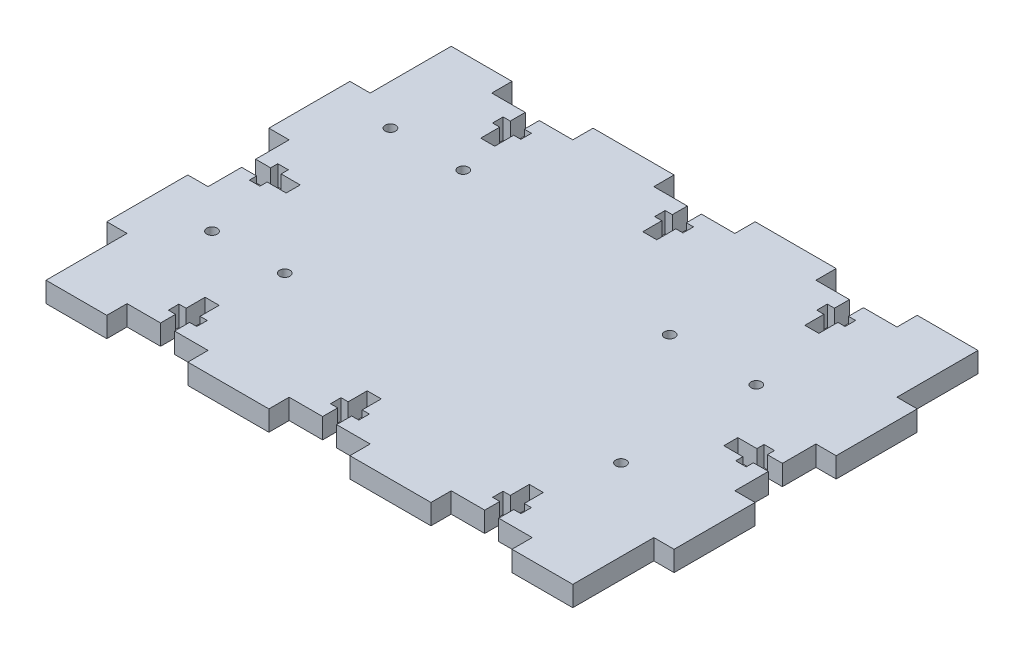
SolidWorks part; units mm, degrees
ref_plane "Front Plane" through (0, 0, 0) normal (0, 0, 1) x (1, 0, 0)
ref_plane "Top Plane" through (0, 0, 0) normal (0, 1, 0) x (1, 0, 0)
ref_plane "Right Plane" through (0, 0, 0) normal (1, 0, 0) x (0, 0, -1)
sketch "Sketch1" plane through (0, 0, 0) normal (0, 1, 0) x (1, 0, 0)
  line L1 (0, 0) -> (177.8, 0)
  line L2 (0, 0) -> (0, 127)
  line L3 (0, 127) -> (177.8, 127)
  line L4 (177.8, 0) -> (177.8, 127)
  dimension "D1" = 127
  dimension "D2" = 177.8
extrude "Boss-Extrude1" add sketch "Sketch1" along normal blind 6.35
sketch "Sketch2" plane through (0, 6.35, 0) normal (0, 1, 0) x (1, 0, 0)
  line L1 (0, 127) -> (6.35, 127)
  line L2 (0, 127) -> (0, 101.6)
  line L3 (0, 101.6) -> (6.35, 101.6)
  line L4 (6.35, 127) -> (6.35, 101.6)
  dimension "D1" = 25.4
  dimension "D2" = 6.35
extrude "Cut-Extrude1" cut sketch "Sketch2" against normal blind 6.35
pattern_linear "LPattern1" count 3 spacing 50.8 along (0, 0, 1) count 2 spacing 171.45 along (1, 0, 0) of "Cut-Extrude1"
sketch "Sketch3" plane through (0, 6.35, 0) normal (0, 1, 0) x (1, 0, 0)
  line L0 (6.35, 0) -> (171.45, 0) construction
  line L1 (25.4, 0) -> (50.8, 0)
  line L2 (25.4, 0) -> (25.4, 6.35)
  line L3 (25.4, 6.35) -> (50.8, 6.35)
  line L4 (50.8, 0) -> (50.8, 6.35)
  line L5 (0, 50.8) -> (0, 25.4) construction
  dimension "D1" = 25.4
  dimension "D2" = 6.35
  dimension "D3" = 25.4
extrude "Cut-Extrude2" cut sketch "Sketch3" against normal blind 6.35
pattern_linear "LPattern2" count 3 spacing 50.8 along (1, 0, 0) count 2 spacing 120.65 along (0, 0, -1) of "Cut-Extrude2"
ref_plane "Plane1" through (0, 0, -63.5) normal (0, 0, 1) x (1, 0, 0)
ref_plane "Plane2" through (88.9, 0, 0) normal (1, 0, 0) x (0, 0, -1)
sketch "Sketch4" plane through (0, 6.35, 0) normal (0, 1, 0) x (1, 0, 0)
  line L0 (171.45, 76.2) -> (171.45, 50.8) construction
  line L1 (171.45, 65.6971) -> (157.48, 65.6971)
  line L2 (171.45, 65.6971) -> (171.45, 61.3029)
  line L3 (171.45, 61.3029) -> (157.48, 61.3029)
  line L4 (157.48, 65.6971) -> (157.48, 61.3029)
  line L5 (177.8, 76.2) -> (171.45, 76.2) construction
  line L7 (163.449, 67.945) -> (166.751, 67.945)
  line L8 (163.449, 67.945) -> (163.449, 59.055)
  line L9 (163.449, 59.055) -> (166.751, 59.055)
  line L10 (166.751, 67.945) -> (166.751, 59.055)
  point P6 (171.45, 63.5)
  point P13 (165.1, 59.055)
  point P14 (166.751, 63.5)
  dimension "D1" = 13.97
  dimension "D2" = 4.3942
  dimension "D3" = 12.7
  dimension "D4" = 3.302
  dimension "D5" = 6.35
  dimension "D6" = 8.89
  dimension "D7" = 12.7
extrude "Cut-Extrude3" cut sketch "Sketch4" against normal blind 8.89 contours L1 L4 L3 L2 | L7 L10 L9 L8
mirror "Mirror1" about plane through (88.9, 0, 0) normal (1, 0, 0) of "Cut-Extrude3"
sketch "Sketch5" plane through (0, 6.35, 0) normal (0, 1, 0) x (1, 0, 0)
  line L0 (50.8, 6.35) -> (25.4, 6.35) construction
  line L1 (35.9029, 6.35) -> (40.2971, 6.35)
  line L2 (35.9029, 6.35) -> (35.9029, 20.32)
  line L3 (35.9029, 20.32) -> (40.2971, 20.32)
  line L4 (40.2971, 6.35) -> (40.2971, 20.32)
  line L5 (50.8, 0) -> (50.8, 6.35) construction
  line L6 (33.655, 14.351) -> (42.545, 14.351)
  line L7 (33.655, 14.351) -> (33.655, 11.049)
  line L8 (33.655, 11.049) -> (42.545, 11.049)
  line L9 (42.545, 14.351) -> (42.545, 11.049)
  point P6 (38.1, 20.32)
  point P12 (38.1, 11.049)
  point P15 (42.545, 12.7)
  dimension "D1" = 13.97
  dimension "D2" = 4.3942
  dimension "D3" = 12.7
  dimension "D4" = 3.302
  dimension "D5" = 8.89
  dimension "D6" = 12.7
  dimension "D7" = 6.35
extrude "Cut-Extrude4" cut sketch "Sketch5" against normal blind 30.48 contours L3 L4 L1 L2 | L7 L8 L9 L6
pattern_linear "LPattern3" count 3 spacing 50.8 along (1, 0, 0) of "Cut-Extrude4"
sketch "Sketch10" plane through (0, 6.35, 0) normal (0, 1, 0) x (1, 0, 0)
  line L0 (0, 101.6) -> (0, 76.2) construction
  line L1 (19.05, 95.25) -> (41.8592, 95.25)
  line L2 (19.05, 95.25) -> (19.05, 39.3192)
  line L3 (19.05, 39.3192) -> (41.8592, 39.3192)
  line L4 (41.8592, 95.25) -> (41.8592, 39.3192)
  line L5 (127, 120.65) -> (152.4, 120.65) construction
  point P6 (0, 88.9)
  dimension "D1" = 22.8092
  dimension "D2" = 55.9308
  dimension "D4" = 19.05
  dimension "D5" = 25.4
mirror "Mirror2" about plane through (0, 0, -63.5) normal (0, 0, 1) of "LPattern3"
hole_wizard "#4 Clearance Hole2" positions "Sketch12" profile "Sketch11" hole size "#4" standard "ANSI Inch"
sketch "Sketch12" plane through (0, 6.35, 0) normal (0, 1, 0) x (1, 0, 0)
  point P0 (19.05, 95.25)
  point P3 (41.8592, 95.25)
  point P6 (41.8592, 39.3192)
  point P9 (19.05, 39.3192)
sketch "Sketch11" plane through (19.05, 6.35, -95.25) normal (1, 0, 0) x (0, 0, 1)
  line L0 (0, 0) -> (0, 11.1406)
  line L1 (0, 11.1406) -> (1.6319, 10.16)
  line L2 (1.6319, 10.16) -> (1.6319, 0)
  line L5 (1.6319, 0) -> (0, 0)
  line L10 (0, 11.1406) -> (-1.6319, 10.16) construction
  line L11 (0, -6.35) -> (0, 107.95) construction
  dimension "Hole Dia." = 3.2639
  dimension "Hole Depth" = 10.16
  dimension "Drill Angle" = 118
sketch "Sketch13" plane through (0, 6.35, 0) normal (0, 1, 0) x (1, 0, 0)
  line L0 (157.48, 65.6971) -> (157.48, 61.3029) construction
  line L1 (107.95, 90.551) -> (158.75, 90.551)
  line L2 (107.95, 90.551) -> (107.95, 36.449)
  line L3 (107.95, 36.449) -> (158.75, 36.449)
  line L4 (158.75, 90.551) -> (158.75, 36.449)
  line L5 (107.95, 90.551) -> (158.75, 36.449) construction
  line L6 (107.95, 36.449) -> (158.75, 90.551) construction
  line L7 (177.8, 76.2) -> (177.8, 101.6) construction
  point P0 (133.35, 63.5)
  point P7 (157.48, 63.5)
  dimension "D1" = 50.8
  dimension "D2" = 54.102
  dimension "D3" = 19.05
hole_wizard "#4 Clearance Hole3" positions "Sketch15" profile "Sketch14" hole size "#4" standard "ANSI Inch"
sketch "Sketch15" plane through (0, 6.35, 0) normal (0, 1, 0) x (1, 0, 0)
  line L0 (107.95, 90.551) -> (158.75, 90.551) construction
  line L3 (107.95, 90.551) -> (107.95, 36.449) construction
  point P0 (118.872, 82.931)
  point P2 (146.05, 82.931)
  point P4 (146.05, 40.513)
  dimension "D1" = 7.62
  dimension "D2" = 10.922
  dimension "D3" = 27.178
  dimension "D4" = 42.418
sketch "Sketch14" plane through (118.872, 6.35, -82.931) normal (1, 0, 0) x (0, 0, 1)
  line L0 (0, 0) -> (0, 11.1406)
  line L1 (0, 11.1406) -> (1.6319, 10.16)
  line L2 (1.6319, 10.16) -> (1.6319, 0)
  line L5 (1.6319, 0) -> (0, 0)
  line L10 (0, 11.1406) -> (-1.632, 10.16) construction
  line L11 (0, -6.35) -> (0, 107.95) construction
  dimension "Hole Dia." = 3.2639
  dimension "Hole Depth" = 10.16
  dimension "Drill Angle" = 118
